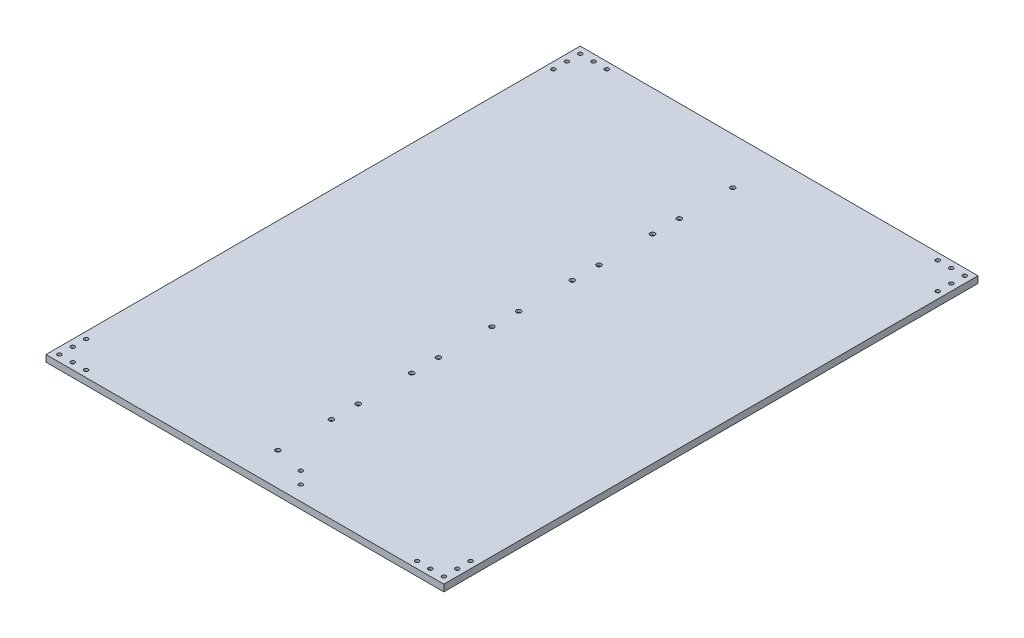
SolidWorks part; units mm, degrees
ref_plane "Front Plane" through (0, 0, 0) normal (0, 0, 1) x (1, 0, 0)
ref_plane "Top Plane" through (0, 0, 0) normal (0, 1, 0) x (1, 0, 0)
ref_plane "Right Plane" through (0, 0, 0) normal (1, 0, 0) x (0, 0, -1)
sketch "Sketch1" plane through (0, 0, 0) normal (0, 1, 0) x (1, 0, 0)
  line L1 (0, 0) -> (297.5, 0)
  line L2 (0, 0) -> (0, 399.5)
  line L3 (0, 399.5) -> (297.5, 399.5)
  line L4 (297.5, 0) -> (297.5, 399.5)
  dimension "D1" = 399.5
  dimension "D2" = 297.5
extrude "Boss-Extrude1" add sketch "Sketch1" along normal blind 5
sketch "Sketch3" plane through (0, 5, 0) normal (0, 1, 0) x (1, 0, 0)
  circle A0 centre (148.7481, 24.6847) radius 1.7499
  circle A1 centre (148.7483, 64.6837) radius 1.7504
  circle A2 centre (148.7504, 84.7207) radius 1.7502
  circle A3 centre (148.748, 124.721) radius 1.7496
  circle A4 centre (148.749, 144.7501) radius 1.751
  circle A5 centre (148.7475, 184.7526) radius 1.7486
  circle A6 centre (148.747, 204.7868) radius 1.7489
  circle A7 centre (148.7482, 244.7868) radius 1.7499
  circle A8 centre (148.747, 264.8168) radius 1.7489
  circle A9 centre (148.7502, 304.8159) radius 1.751
  circle A10 centre (148.747, 324.8528) radius 1.7489
  circle A11 centre (148.751, 364.8529) radius 1.7522
extrude "Cut-Extrude2" cut sketch "Sketch3" against normal blind 10
sketch "Sketch5" plane through (0, 5, 0) normal (0, 1, 0) x (1, 0, 0)
  line L0 (0, 0) -> (297.5, 0) construction
  line L1 (10, 10) -> (287.5, 10)
  line L2 (10, 10) -> (10, 389.5)
  line L3 (10, 389.5) -> (287.5, 389.5)
  line L4 (287.5, 10) -> (287.5, 389.5)
  line L5 (0, 399.5) -> (0, 0) construction
  line L6 (297.5, 399.5) -> (0, 399.5) construction
  line L7 (297.5, 0) -> (297.5, 399.5) construction
  line L8 (0, 199.75) -> (297.5, 199.75)
  line L9 (148.75, 0) -> (148.75, 399.5)
  circle A0 centre (5, 5) radius 1.5
  circle A1 centre (5, 15) radius 1.5
  circle A2 centre (15, 5) radius 1.5
  circle A3 centre (5, 25) radius 1.5
  circle A4 centre (25, 5) radius 1.5
  circle A5 centre (25, 394.5) radius 1.5
  circle A6 centre (15, 394.5) radius 1.5
  circle A7 centre (5, 374.5) radius 1.5
  circle A8 centre (5, 384.5) radius 1.5
  circle A9 centre (5, 394.5) radius 1.5
  circle A10 centre (292.5, 374.5) radius 1.5
  circle A11 centre (292.5, 384.5) radius 1.5
  circle A12 centre (292.5, 394.5) radius 1.5
  circle A13 centre (282.5, 394.5) radius 1.5
  circle A14 centre (272.5, 394.5) radius 1.5
  circle A15 centre (292.5, 25) radius 1.5
  circle A16 centre (292.5, 15) radius 1.5
  circle A17 centre (292.5, 5) radius 1.5
  circle A18 centre (282.5, 5) radius 1.5
  circle A19 centre (272.5, 5) radius 1.5
  dimension "D5" = 3
  dimension "D6" = 5
  dimension "D7" = 5
  dimension "D8" = 3
  dimension "D9" = 3
  dimension "D10" = 3
  dimension "D11" = 3
  dimension "D12" = 5
  dimension "D13" = 5
  dimension "D14" = 5
  dimension "D15" = 5
  dimension "D16" = 10
  dimension "D17" = 10
  dimension "D18" = 10
  dimension "D19" = 10
  dimension "D1" = 10
  dimension "D2" = 10
  dimension "D3" = 10
  dimension "D4" = 10
extrude "Cut-Extrude3" cut sketch "Sketch5" against normal blind 10 contours A19 | A18 | A17 | A16 | A15 | A10 | A11 | A12 | A13 | A14 | A7 | A8 | A9 | A6 | A5 | A4 | A2 | A0 | A1 | A3 region at (5, 5, -5) region at (5, 5, -15) region at (15, 5, -5) region at (5, 5, -25) region at (25, 5, -5) region at (25, 5, -394.5) region at (15, 5, -394.5) region at (5, 5, -374.5) region at (5, 5, -384.5) region at (5, 5, -394.5) region at (292.5, 5, -374.5) region at (292.5, 5, -384.5) region at (292.5, 5, -394.5) region at (282.5, 5, -394.5) region at (272.5, 5, -394.5) region at (292.5, 5, -25) region at (292.5, 5, -15) region at (292.5, 5, -5) region at (282.5, 5, -5) region at (272.5, 5, -5)
sketch "Sketch6" plane through (0, 0, 0) normal (0, -1, 0) x (1, 0, 0)
  line L0 (0, -199.75) -> (297.5, -199.75)
  line L1 (1.2091, -394.5) -> (3.1046, -397.783)
  line L2 (3.1046, -397.783) -> (6.8954, -397.783)
  line L3 (6.8954, -397.783) -> (8.7909, -394.5)
  line L4 (8.7909, -394.5) -> (6.8954, -391.217)
  line L5 (6.8954, -391.217) -> (3.1046, -391.217)
  line L6 (3.1046, -391.217) -> (1.2091, -394.5)
  line L7 (1.2091, -384.5) -> (3.1046, -387.783)
  line L8 (3.1046, -387.783) -> (6.8954, -387.783)
  line L9 (6.8954, -387.783) -> (8.7909, -384.5)
  line L10 (8.7909, -384.5) -> (6.8954, -381.217)
  line L11 (6.8954, -381.217) -> (3.1046, -381.217)
  line L12 (3.1046, -381.217) -> (1.2091, -384.5)
  line L13 (1.2091, -374.5) -> (3.1046, -377.783)
  line L14 (3.1046, -377.783) -> (6.8954, -377.783)
  line L15 (6.8954, -377.783) -> (8.7909, -374.5)
  line L16 (8.7909, -374.5) -> (6.8954, -371.217)
  line L17 (6.8954, -371.217) -> (3.1046, -371.217)
  line L18 (3.1046, -371.217) -> (1.2091, -374.5)
  line L19 (11.2091, -394.5) -> (13.1046, -397.783)
  line L20 (13.1046, -397.783) -> (16.8954, -397.783)
  line L21 (16.8954, -397.783) -> (18.7909, -394.5)
  line L22 (18.7909, -394.5) -> (16.8954, -391.217)
  line L23 (16.8954, -391.217) -> (13.1046, -391.217)
  line L24 (13.1046, -391.217) -> (11.2091, -394.5)
  line L25 (21.2091, -394.5) -> (23.1046, -397.783)
  line L26 (23.1046, -397.783) -> (26.8954, -397.783)
  line L27 (26.8954, -397.783) -> (28.7909, -394.5)
  line L28 (28.7909, -394.5) -> (26.8954, -391.217)
  line L29 (26.8954, -391.217) -> (23.1046, -391.217)
  line L30 (23.1046, -391.217) -> (21.2091, -394.5)
  line L31 (0, -399.5) -> (0, 0) construction
  line L32 (297.5, 0) -> (297.5, -399.5) construction
  line L33 (3.1046, -28.283) -> (1.2091, -25)
  line L34 (6.8954, -28.283) -> (3.1046, -28.283)
  line L35 (8.7909, -25) -> (6.8954, -28.283)
  line L36 (6.8954, -21.717) -> (8.7909, -25)
  line L37 (3.1046, -21.717) -> (6.8954, -21.717)
  line L38 (1.2091, -25) -> (3.1046, -21.717)
  line L39 (3.1046, -18.283) -> (1.2091, -15)
  line L40 (6.8954, -18.283) -> (3.1046, -18.283)
  line L41 (8.7909, -15) -> (6.8954, -18.283)
  line L42 (6.8954, -11.717) -> (8.7909, -15)
  line L43 (3.1046, -11.717) -> (6.8954, -11.717)
  line L44 (1.2091, -15) -> (3.1046, -11.717)
  line L45 (3.1046, -8.283) -> (1.2091, -5)
  line L46 (6.8954, -8.283) -> (3.1046, -8.283)
  line L47 (8.7909, -5) -> (6.8954, -8.283)
  line L48 (6.8954, -1.717) -> (8.7909, -5)
  line L49 (3.1046, -1.717) -> (6.8954, -1.717)
  line L50 (1.2091, -5) -> (3.1046, -1.717)
  line L51 (13.1046, -8.283) -> (11.2091, -5)
  line L52 (16.8954, -8.283) -> (13.1046, -8.283)
  line L53 (18.7909, -5) -> (16.8954, -8.283)
  line L54 (16.8954, -1.717) -> (18.7909, -5)
  line L55 (13.1046, -1.717) -> (16.8954, -1.717)
  line L56 (11.2091, -5) -> (13.1046, -1.717)
  line L57 (23.1046, -8.283) -> (21.2091, -5)
  line L58 (26.8954, -8.283) -> (23.1046, -8.283)
  line L59 (28.7909, -5) -> (26.8954, -8.283)
  line L60 (26.8954, -1.717) -> (28.7909, -5)
  line L61 (23.1046, -1.717) -> (26.8954, -1.717)
  line L62 (21.2091, -5) -> (23.1046, -1.717)
  line L63 (148.75, -399.5) -> (148.75, 0)
  line L64 (297.5, -399.5) -> (0, -399.5) construction
  line L65 (0, 0) -> (297.5, 0) construction
  line L66 (270.6046, -8.283) -> (274.3954, -8.283)
  line L67 (268.7091, -5) -> (270.6046, -8.283)
  line L68 (270.6046, -1.717) -> (268.7091, -5)
  line L69 (274.3954, -1.717) -> (270.6046, -1.717)
  line L70 (276.2909, -5) -> (274.3954, -1.717)
  line L71 (274.3954, -8.283) -> (276.2909, -5)
  line L72 (280.6046, -8.283) -> (284.3954, -8.283)
  line L73 (278.7091, -5) -> (280.6046, -8.283)
  line L74 (280.6046, -1.717) -> (278.7091, -5)
  line L75 (284.3954, -1.717) -> (280.6046, -1.717)
  line L76 (286.2909, -5) -> (284.3954, -1.717)
  line L77 (284.3954, -8.283) -> (286.2909, -5)
  line L78 (290.6046, -8.283) -> (294.3954, -8.283)
  line L79 (288.7091, -5) -> (290.6046, -8.283)
  line L80 (290.6046, -1.717) -> (288.7091, -5)
  line L81 (294.3954, -1.717) -> (290.6046, -1.717)
  line L82 (296.2909, -5) -> (294.3954, -1.717)
  line L83 (294.3954, -8.283) -> (296.2909, -5)
  line L84 (290.6046, -18.283) -> (294.3954, -18.283)
  line L85 (288.7091, -15) -> (290.6046, -18.283)
  line L86 (290.6046, -11.717) -> (288.7091, -15)
  line L87 (294.3954, -11.717) -> (290.6046, -11.717)
  line L88 (296.2909, -15) -> (294.3954, -11.717)
  line L89 (294.3954, -18.283) -> (296.2909, -15)
  line L90 (290.6046, -28.283) -> (294.3954, -28.283)
  line L91 (288.7091, -25) -> (290.6046, -28.283)
  line L92 (290.6046, -21.717) -> (288.7091, -25)
  line L93 (294.3954, -21.717) -> (290.6046, -21.717)
  line L94 (296.2909, -25) -> (294.3954, -21.717)
  line L95 (294.3954, -28.283) -> (296.2909, -25)
  line L96 (294.3954, -371.217) -> (296.2909, -374.5)
  line L97 (290.6046, -371.217) -> (294.3954, -371.217)
  line L98 (288.7091, -374.5) -> (290.6046, -371.217)
  line L99 (290.6046, -377.783) -> (288.7091, -374.5)
  line L100 (294.3954, -377.783) -> (290.6046, -377.783)
  line L101 (296.2909, -374.5) -> (294.3954, -377.783)
  line L102 (294.3954, -381.217) -> (296.2909, -384.5)
  line L103 (290.6046, -381.217) -> (294.3954, -381.217)
  line L104 (288.7091, -384.5) -> (290.6046, -381.217)
  line L105 (290.6046, -387.783) -> (288.7091, -384.5)
  line L106 (294.3954, -387.783) -> (290.6046, -387.783)
  line L107 (296.2909, -384.5) -> (294.3954, -387.783)
  line L108 (294.3954, -391.217) -> (296.2909, -394.5)
  line L109 (290.6046, -391.217) -> (294.3954, -391.217)
  line L110 (288.7091, -394.5) -> (290.6046, -391.217)
  line L111 (290.6046, -397.783) -> (288.7091, -394.5)
  line L112 (294.3954, -397.783) -> (290.6046, -397.783)
  line L113 (296.2909, -394.5) -> (294.3954, -397.783)
  line L114 (284.3954, -391.217) -> (286.2909, -394.5)
  line L115 (280.6046, -391.217) -> (284.3954, -391.217)
  line L116 (278.7091, -394.5) -> (280.6046, -391.217)
  line L117 (280.6046, -397.783) -> (278.7091, -394.5)
  line L118 (284.3954, -397.783) -> (280.6046, -397.783)
  line L119 (286.2909, -394.5) -> (284.3954, -397.783)
  line L120 (274.3954, -391.217) -> (276.2909, -394.5)
  line L121 (270.6046, -391.217) -> (274.3954, -391.217)
  line L122 (268.7091, -394.5) -> (270.6046, -391.217)
  line L123 (270.6046, -397.783) -> (268.7091, -394.5)
  line L124 (274.3954, -397.783) -> (270.6046, -397.783)
  line L125 (276.2909, -394.5) -> (274.3954, -397.783)
  circle A0 centre (5, -394.5) radius 3.283 construction
  circle A1 centre (5, -384.5) radius 3.283 construction
  circle A2 centre (5, -374.5) radius 3.283 construction
  circle A3 centre (15, -394.5) radius 3.283 construction
  circle A4 centre (25, -394.5) radius 3.283 construction
  circle M63 centre (282.5, -5) radius 1.5
  circle M64 centre (292.5, -5) radius 1.5
  circle M65 centre (292.5, -15) radius 1.5
  circle M66 centre (292.5, -25) radius 1.5
  circle M67 centre (25, -394.5) radius 1.5
  circle M68 centre (15, -394.5) radius 1.5
  circle M69 centre (5, -374.5) radius 1.5
  circle M70 centre (5, -384.5) radius 1.5
  circle M71 centre (5, -394.5) radius 1.5
  circle M72 centre (272.5, -5) radius 1.5
  circle M89 centre (5, -25) radius 1.5
  circle M90 centre (5, -15) radius 1.5
  circle M91 centre (5, -5) radius 1.5
  circle M92 centre (272.5, -394.5) radius 1.5
  circle M93 centre (25, -5) radius 1.5
  circle M94 centre (15, -5) radius 1.5
  circle M95 centre (282.5, -394.5) radius 1.5
  circle M96 centre (292.5, -394.5) radius 1.5
  circle M97 centre (292.5, -384.5) radius 1.5
  circle M98 centre (292.5, -374.5) radius 1.5
  dimension "D1" = 7.5818
  dimension "D2" = 7.5818
  dimension "D3" = 7.5818
  dimension "D4" = 7.5818
  dimension "D5" = 7.5818
extrude "Cut-Extrude4" cut sketch "Sketch6" against normal blind 3 contours L119 L114 L115 L116 L117 L118 M95 | L125 L120 L121 L122 L123 L124 M92 | L113 L108 L109 L110 L111 L112 M96 | L107 L102 L103 L104 L105 L106 M97 | L101 L96 L97 L98 L99 L100 M98 | L5 L6 L1 L2 L3 L4 M71 | L23 L24 L19 L20 L21 L22 M68 | L29 L30 L25 L26 L27 L28 M67 | L11 L12 L7 L8 L9 L10 M70 | L17 L18 L13 L14 L15 L16 M69 | L38 L33 L34 L35 L36 L37 M89 | L44 L39 L40 L41 L42 L43 M90 | L50 L45 L46 L47 L48 L49 M91 | L56 L51 L52 L53 L54 L55 M94 | L62 L57 L58 L59 L60 L61 M93 | L66 L71 L70 L69 L68 L67 M72 | L72 L77 L76 L75 L74 L73 M63 | L78 L83 L82 L81 L80 L79 M64 | L84 L89 L88 L87 L86 L85 M65 | L90 L95 L94 L93 L92 L91 M66 region at (2.2437, 0, -392.9086) region at (2.2437, 0, -382.9086) region at (2.2437, 0, -372.9086) region at (12.2437, 0, -392.9086) region at (22.2437, 0, -392.9086) region at (2.2437, 0, -26.5914) region at (2.2437, 0, -16.5914) region at (2.2437, 0, -6.5914) region at (12.2437, 0, -6.5914) region at (22.2437, 0, -6.5914) region at (269.7437, 0, -6.5914) region at (279.7437, 0, -6.5914) region at (289.7437, 0, -6.5914) region at (289.7437, 0, -16.5914) region at (289.7437, 0, -26.5914) region at (295.2563, 0, -372.9086) region at (295.2563, 0, -382.9086) region at (295.2563, 0, -392.9086) region at (285.2563, 0, -392.9086) region at (275.2563, 0, -392.9086)
sketch "Sketch7" plane through (0, 0, 0) normal (0, -1, 0) x (1, 0, 0)
  line L1 (152.5419, -364.8529) -> (150.6465, -361.5698)
  line L2 (150.6465, -361.5698) -> (146.8556, -361.5698)
  line L3 (146.8556, -361.5698) -> (144.9601, -364.8529)
  line L4 (144.9601, -364.8529) -> (146.8556, -368.1359)
  line L5 (146.8556, -368.1359) -> (150.6465, -368.1359)
  line L6 (150.6465, -368.1359) -> (152.5419, -364.8529)
  line L7 (152.5379, -324.8528) -> (150.6425, -321.5698)
  line L8 (150.6425, -321.5698) -> (146.8516, -321.5698)
  line L9 (146.8516, -321.5698) -> (144.9561, -324.8528)
  line L10 (144.9561, -324.8528) -> (146.8516, -328.1358)
  line L11 (146.8516, -328.1358) -> (150.6425, -328.1358)
  line L12 (150.6425, -328.1358) -> (152.5379, -324.8528)
  line L13 (152.5411, -304.8159) -> (150.6457, -301.5328)
  line L14 (150.6457, -301.5328) -> (146.8548, -301.5328)
  line L15 (146.8548, -301.5328) -> (144.9593, -304.8159)
  line L16 (144.9593, -304.8159) -> (146.8548, -308.0989)
  line L17 (146.8548, -308.0989) -> (150.6457, -308.0989)
  line L18 (150.6457, -308.0989) -> (152.5411, -304.8159)
  line L19 (152.5379, -264.8168) -> (150.6424, -261.5338)
  line L20 (150.6424, -261.5338) -> (146.8516, -261.5338)
  line L21 (146.8516, -261.5338) -> (144.9561, -264.8168)
  line L22 (144.9561, -264.8168) -> (146.8516, -268.0999)
  line L23 (146.8516, -268.0999) -> (150.6424, -268.0999)
  line L24 (150.6424, -268.0999) -> (152.5379, -264.8168)
  line L25 (152.5391, -244.7868) -> (150.6437, -241.5038)
  line L26 (150.6437, -241.5038) -> (146.8528, -241.5038)
  line L27 (146.8528, -241.5038) -> (144.9573, -244.7868)
  line L28 (144.9573, -244.7868) -> (146.8528, -248.0698)
  line L29 (146.8528, -248.0698) -> (150.6437, -248.0698)
  line L30 (150.6437, -248.0698) -> (152.5391, -244.7868)
  line L31 (152.539, -24.6847) -> (150.6435, -21.4017)
  line L32 (150.6435, -21.4017) -> (146.8526, -21.4017)
  line L33 (146.8526, -21.4017) -> (144.9572, -24.6847)
  line L34 (144.9572, -24.6847) -> (146.8526, -27.9678)
  line L35 (146.8526, -27.9678) -> (150.6435, -27.9678)
  line L36 (150.6435, -27.9678) -> (152.539, -24.6847)
  line L37 (152.5392, -64.6837) -> (150.6438, -61.4007)
  line L38 (150.6438, -61.4007) -> (146.8529, -61.4007)
  line L39 (146.8529, -61.4007) -> (144.9574, -64.6837)
  line L40 (144.9574, -64.6837) -> (146.8529, -67.9667)
  line L41 (146.8529, -67.9667) -> (150.6438, -67.9667)
  line L42 (150.6438, -67.9667) -> (152.5392, -64.6837)
  line L43 (152.5413, -84.7207) -> (150.6459, -81.4377)
  line L44 (150.6459, -81.4377) -> (146.855, -81.4377)
  line L45 (146.855, -81.4377) -> (144.9595, -84.7207)
  line L46 (144.9595, -84.7207) -> (146.855, -88.0037)
  line L47 (146.855, -88.0037) -> (150.6459, -88.0037)
  line L48 (150.6459, -88.0037) -> (152.5413, -84.7207)
  line L49 (152.5389, -124.721) -> (150.6435, -121.438)
  line L50 (150.6435, -121.438) -> (146.8526, -121.438)
  line L51 (146.8526, -121.438) -> (144.9571, -124.721)
  line L52 (144.9571, -124.721) -> (146.8526, -128.004)
  line L53 (146.8526, -128.004) -> (150.6435, -128.004)
  line L54 (150.6435, -128.004) -> (152.5389, -124.721)
  line L55 (152.5399, -144.7501) -> (150.6445, -141.4671)
  line L56 (150.6445, -141.4671) -> (146.8536, -141.4671)
  line L57 (146.8536, -141.4671) -> (144.9581, -144.7501)
  line L58 (144.9581, -144.7501) -> (146.8536, -148.0331)
  line L59 (146.8536, -148.0331) -> (150.6445, -148.0331)
  line L60 (150.6445, -148.0331) -> (152.5399, -144.7501)
  line L61 (152.5384, -184.7526) -> (150.643, -181.4696)
  line L62 (150.643, -181.4696) -> (146.8521, -181.4696)
  line L63 (146.8521, -181.4696) -> (144.9566, -184.7526)
  line L64 (144.9566, -184.7526) -> (146.8521, -188.0356)
  line L65 (146.8521, -188.0356) -> (150.643, -188.0356)
  line L66 (150.643, -188.0356) -> (152.5384, -184.7526)
  line L67 (152.5379, -204.7868) -> (150.6425, -201.5038)
  line L68 (150.6425, -201.5038) -> (146.8516, -201.5038)
  line L69 (146.8516, -201.5038) -> (144.9561, -204.7868)
  line L70 (144.9561, -204.7868) -> (146.8516, -208.0698)
  line L71 (146.8516, -208.0698) -> (150.6425, -208.0698)
  line L72 (150.6425, -208.0698) -> (152.5379, -204.7868)
  circle A0 centre (148.751, -364.8529) radius 3.283 construction
  circle A1 centre (148.747, -324.8528) radius 3.283 construction
  circle A2 centre (148.7502, -304.8159) radius 3.283 construction
  circle A3 centre (148.747, -264.8168) radius 3.283 construction
  circle A4 centre (148.7482, -244.7868) radius 3.283 construction
  circle A5 centre (148.7481, -24.6847) radius 3.283 construction
  circle A6 centre (148.7483, -64.6837) radius 3.283 construction
  circle A7 centre (148.7504, -84.7207) radius 3.283 construction
  circle A8 centre (148.748, -124.721) radius 3.283 construction
  circle A9 centre (148.749, -144.7501) radius 3.283 construction
  circle A10 centre (148.7475, -184.7526) radius 3.283 construction
  circle A11 centre (148.747, -204.7868) radius 3.283 construction
  dimension "D1" = 7.5818
  dimension "D2" = 7.5818
  dimension "D3" = 7.5818
  dimension "D4" = 7.5818
  dimension "D5" = 7.5818
  dimension "D6" = 7.5818
  dimension "D7" = 7.5818
  dimension "D8" = 7.5818
  dimension "D9" = 7.5818
  dimension "D10" = 7.5818
  dimension "D11" = 7.5818
  dimension "D12" = 7.5818
extrude "Cut-Extrude5" cut sketch "Sketch7" against normal blind 3
sketch "Sketch13" plane through (0, 5, 0) normal (0, 1, 0) x (1, 0, 0)
  line L0 (0, 0) -> (297.5, 0) construction
  line L1 (297.5, 0) -> (297.5, 399.5) construction
  circle A0 centre (170.5, 20) radius 1.5
  circle A1 centre (179.5, 11) radius 1.5
  dimension "D1" = 3
  dimension "D2" = 3
  dimension "D3" = 11
  dimension "D4" = 118
  dimension "D5" = 127
  dimension "D6" = 20
extrude "Cut-Extrude6" cut sketch "Sketch13" against normal blind 5
sketch "Sketch14" plane through (0, 0, 0) normal (0, -1, 0) x (1, 0, 0)
  line L1 (181.5249, -14.2048) -> (183.2879, -10.8488)
  line L2 (183.2879, -10.8488) -> (181.263, -7.644)
  line L3 (181.263, -7.644) -> (177.4751, -7.7952)
  line L4 (177.4751, -7.7952) -> (175.7121, -11.1512)
  line L5 (175.7121, -11.1512) -> (177.737, -14.356)
  line L6 (177.737, -14.356) -> (181.5249, -14.2048)
  line L7 (172.5249, -23.2048) -> (174.2879, -19.8488)
  line L8 (174.2879, -19.8488) -> (172.263, -16.644)
  line L9 (172.263, -16.644) -> (168.4751, -16.7952)
  line L10 (168.4751, -16.7952) -> (166.7121, -20.1512)
  line L11 (166.7121, -20.1512) -> (168.737, -23.356)
  line L12 (168.737, -23.356) -> (172.5249, -23.2048)
  circle A0 centre (179.5, -11) radius 3.283 construction
  circle A1 centre (170.5, -20) radius 3.283 construction
  dimension "D1" = 7.5818
  dimension "D2" = 7.5818
extrude "Cut-Extrude7" cut sketch "Sketch14" against normal blind 3
